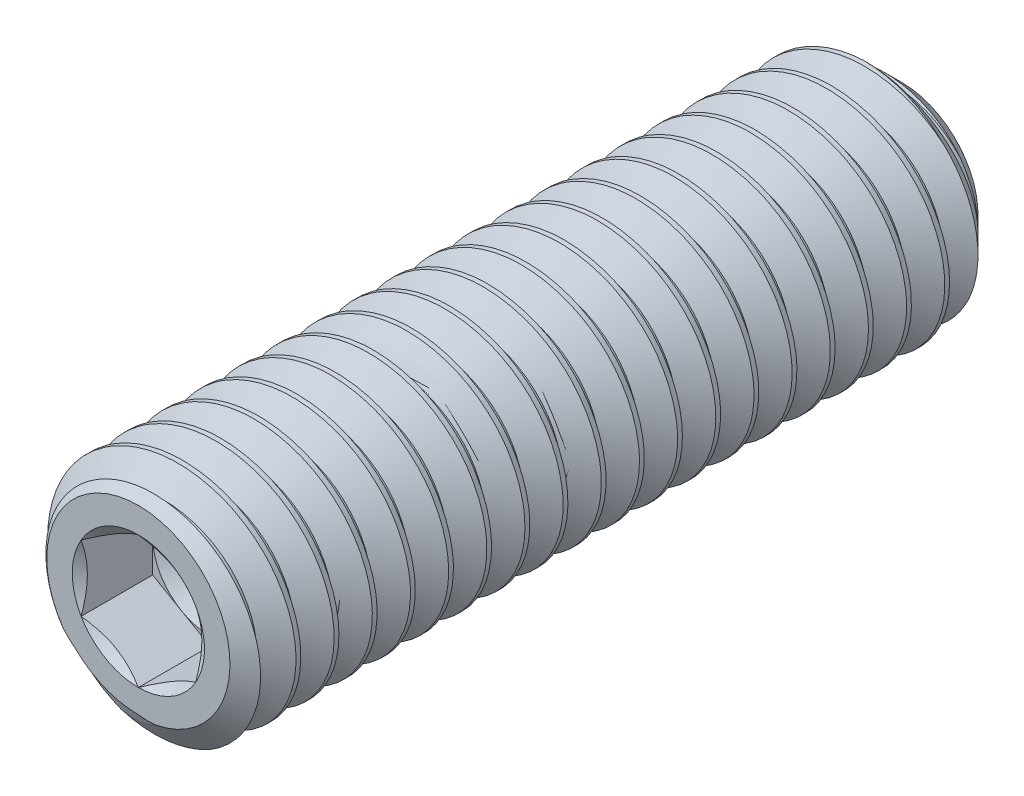
SolidWorks part; units mm, degrees
ref_plane "Front" through (0, 0, 0) normal (0, 0, 1) x (1, 0, 0)
ref_plane "Top" through (0, 0, 0) normal (0, 1, 0) x (1, 0, 0)
ref_plane "Right" through (0, 0, 0) normal (1, 0, 0) x (0, 0, -1)
sketch "Sketch22" plane through (0, 0, 0) normal (1, 0, 0) x (0, 0, -1)
  line L0 (-5, 0) -> (-5, 1.2)
  line L1 (-5, 1.2) -> (-4.7899, 1.5)
  line L2 (-4.7899, 1.5) -> (4.5, 1.5)
  line L3 (4.5, 1.5) -> (5, 1)
  line L4 (-0.145, 1.5) -> (-0.145, -1.5) construction
  line L5 (5, 0) -> (-5, 0)
  line L6 (-5, 1.2) -> (-5, -1.2) construction
  line L7 (5, 0) -> (5, 1)
  point P11 (-0.145, 0)
  dimension "Length" = 10
  dimension "D3" = 35
  dimension "D6" = 45
  dimension "Dia" = 3
  dimension "D1" = 2.4
  dimension "D2" = 0.5
revolve "Revolve1" add sketch "Sketch22" angle 360 about L5
ref_plane "Plane1" through (0, 0, -5) normal (0, 0, 1) x (1, 0, 0)
sketch "Sketch27" plane through (0, 0, -5) normal (0, 0, 1) x (1, 0, 0)
  circle A0 centre (0, 0) radius 1.5 construction
  circle A1 centre (0, 0) radius 1.5
curve "Helix/Spiral1" pitch 0.5 height 10.5 radius 1.5 centre (0, 0, -5) axis (0, 0, 1) start towards (0, 1, 0)
sketch "Sketch28" plane through (0, 0, 0) normal (1, 0, 0) x (0, 0, -1)
  line L0 (5, 1.5) -> (5.4375, 1.5)
  line L1 (5.4375, 1.5) -> (5.25, 1.1752)
  line L2 (5.25, 1.1752) -> (5.1875, 1.1752)
  line L3 (5.1875, 1.1752) -> (5, 1.5)
  line L4 (5.0937, 1.3376) -> (5.3437, 1.3376) construction
  line L6 (-4.7899, 1.5) -> (4.5, 1.5) construction
  dimension "D1" = 0.0625
  dimension "D3" = 60
  dimension "D2" = 0.25
sweep "Cut-Sweep2" cut profiles "Sketch28" path "Helix/Spiral1" align with end faces yes
sketch "Sketch23" plane through (0, 0, 5) normal (0, 0, 1) x (1, 0, 0)
  line L1 (0, 0.866) -> (-0.75, 0.433)
  line L2 (-0.75, 0.433) -> (-0.75, -0.433)
  line L3 (-0.75, -0.433) -> (0, -0.866)
  line L4 (0, -0.866) -> (0.75, -0.433)
  line L5 (0.75, -0.433) -> (0.75, 0.433)
  line L6 (0.75, 0.433) -> (0, 0.866)
  circle A0 centre (0, 0) radius 0.75 construction
  dimension "Hex" = 1.5
extrude "Cut-Extrude10" cut sketch "Sketch23" against normal blind 0.9375
sketch "Sketch24" plane through (0, 0, 5) normal (0, 0, 1) x (1, 0, 0)
  circle A0 centre (0, 0) radius 0.866
extrude "Cut-Extrude11" cut sketch "Sketch24" against normal through all draft 55
sketch "Sketch26" plane through (0, 0, 4.0625) normal (0, 0, 1) x (1, 0, 0)
  circle A0 centre (0, 0) radius 0.75 construction
  circle A1 centre (0, 0) radius 0.75
extrude "Cut-Extrude12" cut sketch "Sketch26" against normal through all draft 60
sketch "Sketch30" plane through (0, 0, 0) normal (1, 0, 0) x (0, 0, -1)
  line L0 (-4.7899, 1.5) -> (4.5, 1.5) construction
  line L1 (-5, 0) -> (-5, 1.2) construction
  line L2 (5, 0) -> (5, 1) construction
  point P0 (-5, 1.5)
  point P1 (5, 1.5)
  point P2 (5, -1.5)
  point P11 (3.75, -1.5)
  dimension "D1" = 1.25
equation "\"D1@Sketch28\" = \"D4@Helix/Spiral1\" * .125"
equation "\"D2@Sketch28\" = \"D4@Helix/Spiral1\" * .5"
equation "\"D3@Helix/Spiral1\" = \"Length@Sketch22\" + \"D4@Helix/Spiral1\""
equation "\"D1@Sketch30\" = \"D4@Helix/Spiral1\" * 2.5"
equation "\"hex Depth@Cut-Extrude10\" = \"Hex@Sketch23\" * .625"
equation "\"D1@Sketch22\" = \"Dia@Sketch22\" * .8"
equation "\"D2@Sketch22\" = \"D4@Helix/Spiral1\""
